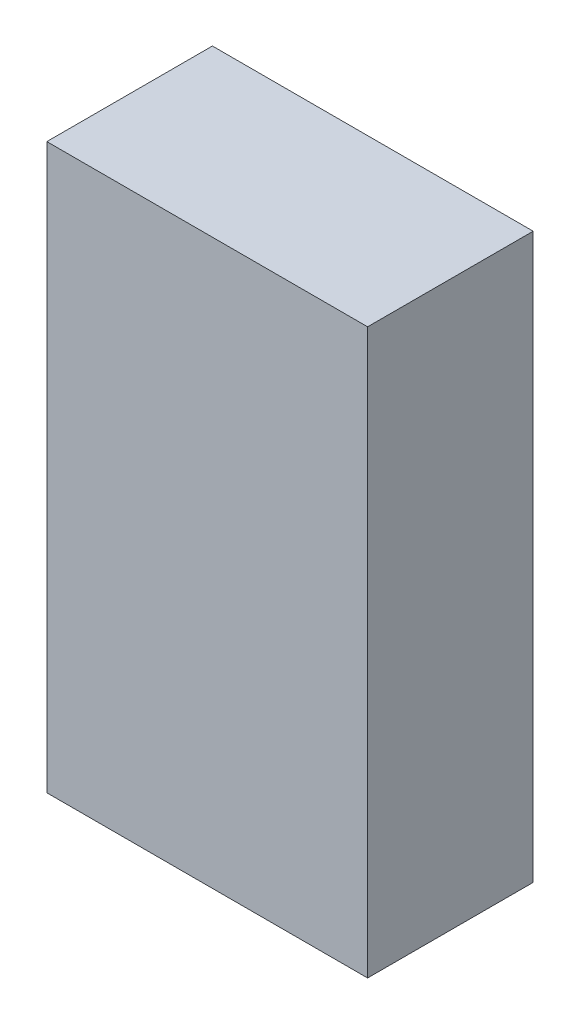
SolidWorks part; units mm, degrees
material "Manual Density from Real Component Mass Battery LiHV"
ref_plane "Piano frontale" through (0, 0, 0) normal (0, 0, 1) x (1, 0, 0)
ref_plane "Piano superiore" through (0, 0, 0) normal (0, 1, 0) x (1, 0, 0)
ref_plane "Piano destro" through (0, 0, 0) normal (1, 0, 0) x (0, 0, -1)
sketch "Schizzo1" plane through (0, 0, 0) normal (0, 0, 1) x (1, 0, 0)
  line L1 (31, 54.5) -> (-31, 54.5)
  line L2 (31, 54.5) -> (31, -54.5)
  line L3 (31, -54.5) -> (-31, -54.5)
  line L4 (-31, 54.5) -> (-31, -54.5)
  line L5 (31, 54.5) -> (-31, -54.5) construction
  line L6 (31, -54.5) -> (-31, 54.5) construction
  point P0 (0, 0)
  dimension "D1" = 109
  dimension "D2" = 62
extrude "Estrusione-Estrusione1" add sketch "Schizzo1" along normal blind 16 and the other way blind 16
